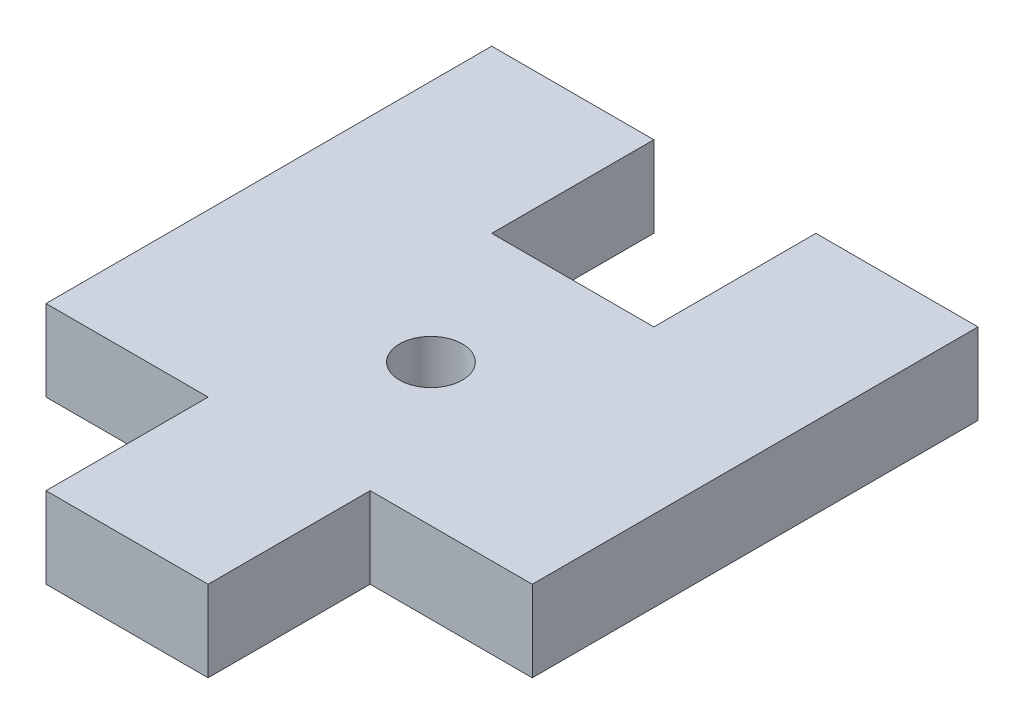
SolidWorks part; units mm, degrees
ref_plane "前基準面" through (0, 0, 0) normal (0, 0, 1) x (1, 0, 0)
ref_plane "上基準面" through (0, 0, 0) normal (0, 1, 0) x (1, 0, 0)
ref_plane "右基準面" through (0, 0, 0) normal (1, 0, 0) x (0, 0, -1)
sketch "草圖1" plane through (0, 0, 0) normal (0, 1, 0) x (1, 0, 0)
  line L1 (-12, 15) -> (12, 15)
  line L2 (-12, 15) -> (-12, -15)
  line L3 (-12, -15) -> (12, -15)
  line L4 (12, 15) -> (12, -15)
  line L5 (-12, 15) -> (12, -15) construction
  line L6 (-12, -15) -> (12, 15) construction
  point P0 (0, 0)
  point P6 (0, 0)
  point P7 (0, -54)
  dimension "D1" = 24
  dimension "D2" = 15
  dimension "D3" = 54
  dimension "D4" = 39
extrude "填料-伸長1" add sketch "草圖1" along normal blind 4
sketch "草圖3" plane through (0, 4, 0) normal (0, 1, 0) x (1, 0, 0)
  line L0 (0, 15) -> (0, -15) construction
  line L1 (-12, 15) -> (-4, 15)
  line L2 (-12, 15) -> (-12, 7)
  line L3 (-12, 7) -> (-4, 7)
  line L4 (-4, 15) -> (-4, 7)
  line L5 (12, 15) -> (-12, 15) construction
  line L6 (-12, -15) -> (12, -15) construction
  line L7 (12, 7) -> (4, 7)
  line L8 (4, 15) -> (4, 7)
  line L9 (12, 15) -> (4, 15)
  line L10 (12, 15) -> (12, 7)
  line L11 (12, 0) -> (-12, 0) construction
  line L12 (12, -15) -> (12, 15) construction
  line L13 (-12, 15) -> (-12, -15) construction
  line L14 (-12, -7) -> (-4, -7)
  line L15 (-4, -15) -> (-4, -7)
  line L16 (-12, -15) -> (-4, -15)
  line L17 (-12, -15) -> (-12, -7)
  line L18 (12, -15) -> (12, -7)
  line L19 (12, -15) -> (4, -15)
  line L20 (4, -15) -> (4, -7)
  line L21 (12, -7) -> (4, -7)
  dimension "D1" = 8
  dimension "D2" = 8
sketch "草圖4" plane through (0, 4, 0) normal (0, 1, 0) x (1, 0, 0)
  line L13 (-4, 15) -> (4, 15)
  line L14 (-4, 15) -> (-4, 7)
  line L15 (-4, 7) -> (4, 7)
  line L16 (4, 15) -> (4, 7)
  line L17 (-12, -7) -> (-4, -7)
  line L18 (-12, -7) -> (-12, -15)
  line L19 (-12, -15) -> (-4, -15)
  line L20 (-4, -7) -> (-4, -15)
  line L21 (4, -7) -> (12, -7)
  line L22 (4, -7) -> (4, -15)
  line L23 (4, -15) -> (12, -15)
  line L24 (12, -7) -> (12, -15)
extrude "除料-伸長3" cut sketch "草圖4" against normal through all
sketch "草圖7" plane through (0, 4, 0) normal (0, 1, 0) x (1, 0, 0)
  point P0 (0, 0)
hole_wizard "Ø3.1 (3.1) 直徑孔1" positions "3D草圖4" profile "草圖9" hole size "Ø3.1" standard "ISO" end condition through all
sketch3d "3D草圖4"
  point P0 (0, 4, 0)
sketch "草圖9" plane through (0, 4, 0) normal (1, 0, 0) x (0, 0, 1)
  line L0 (0, 0) -> (0, 4)
  line L1 (0, 4) -> (1.55, 4)
  line L2 (1.55, 4) -> (1.55, 0)
  line L5 (1.55, 0) -> (0, 0)
  line L11 (0, -6.35) -> (0, 107.95) construction
  dimension "貫穿孔直徑" = 3.1
  dimension "貫穿孔深度" = 4
